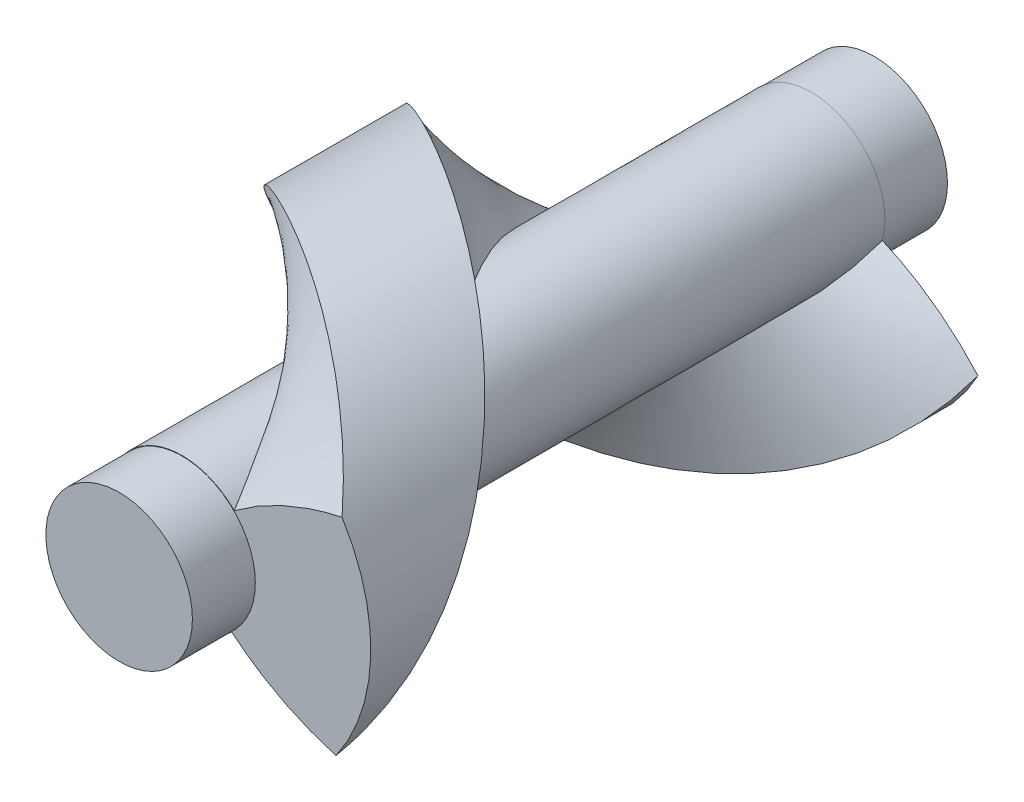
SolidWorks part; units mm, degrees
ref_plane "前视基准面" through (0, 0, 0) normal (0, 0, 1) x (1, 0, 0)
ref_plane "上视基准面" through (0, 0, 0) normal (0, 1, 0) x (1, 0, 0)
ref_plane "右视基准面" through (0, 0, 0) normal (1, 0, 0) x (0, 0, -1)
sketch "草图1" plane through (0, 0, 0) normal (0, 0, 1) x (1, 0, 0)
  circle A0 centre (0, 0) radius 30
curve "螺旋线/涡状线1" pitch 120 height 120 radius 30 left hand yes centre (0, 0, 0) axis (0, 0, 1) start towards (-1, 0, 0)
sketch "草图2" plane through (0, 0, 0) normal (0, 0, 1) x (1, 0, 0)
  circle A0 centre (0, 0) radius 30
curve "螺旋线/涡状线2" pitch 120 height 240 turns 2
extrude "凸台-拉伸1" add sketch "草图1<2>" along normal blind 120
sketch "草图1<2>" plane through (0, 0, 0) normal (0, 0, 1) x (1, 0, 0) same geometry as "草图1"
sketch "草图4" plane through (0, 0, 0) normal (0, 1, 0) x (1, 0, 0)
  line L0 (-30, 49.3231) -> (-30, -48.2003)
  line L1 (-30, 0) -> (-30, -120) construction
  line L2 (-30, -48.2003) -> (-11.7053, -44.1099)
  line L3 (-11.7053, -44.1099) -> (-11.7053, 45.0388)
  line L6 (-30, 49.3231) -> (-11.7053, 45.0388)
  point P0 (-11.7053, 45.0388)
sweep "切除-扫描1" cut profiles "草图4" path "螺旋线/涡状线1" align with end faces yes
sketch "草图5" plane through (0, 0, 0) normal (0, 0, 1) x (1, 0, 0)
  circle A0 centre (0, 0) radius 30
extrude "切除-拉伸1" cut sketch "草图5" against normal blind 20 and the other way blind 20 contours A0
sketch "草图9" plane through (0, 0, 20) normal (0, 0, -1) x (-1, 0, 0)
  circle A0 centre (0, 0) radius 11.6453
extrude "凸台-拉伸2" add sketch "草图9" along normal blind 10
sketch "草图10" plane through (0, 0, 120) normal (0, 0, 1) x (1, 0, 0)
  circle A0 centre (0, 0) radius 11.6453
extrude "凸台-拉伸3" add sketch "草图10" along normal blind 10
